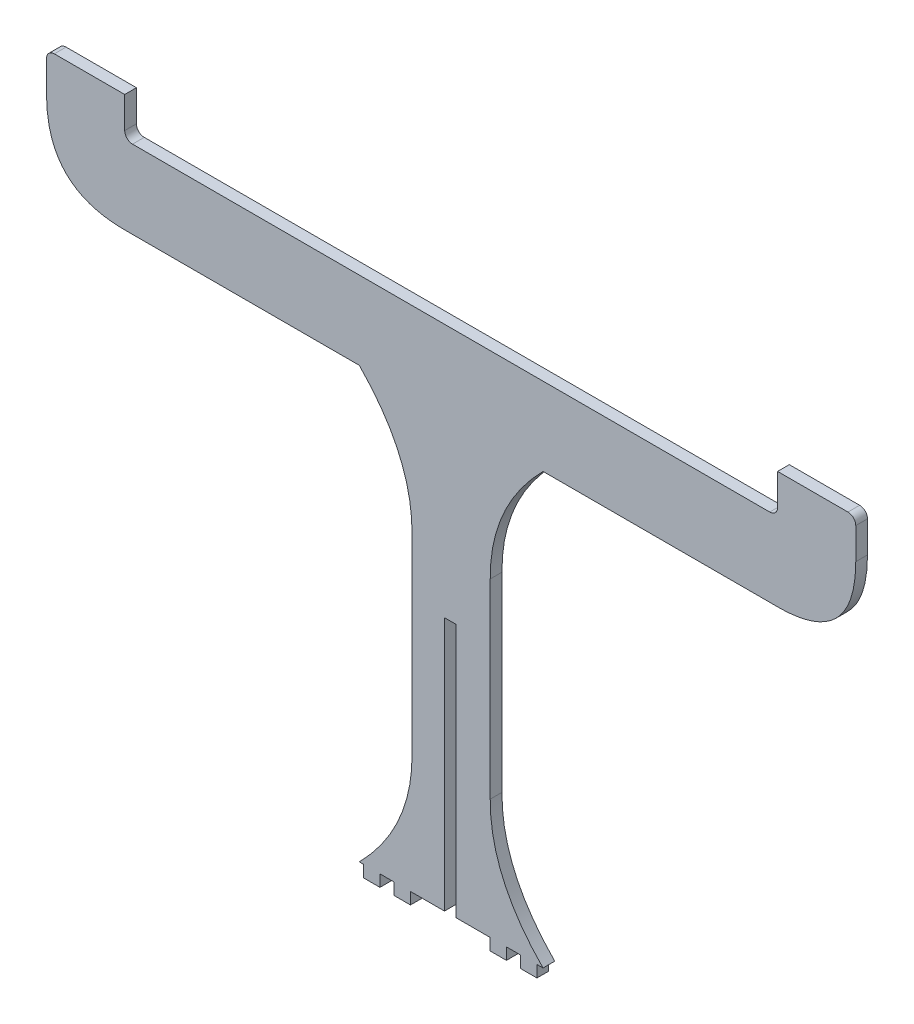
SolidWorks part; units mm, degrees
ref_plane "Přední rovina" through (0, 0, 0) normal (0, 0, 1) x (1, 0, 0)
ref_plane "Horní rovina" through (0, 0, 0) normal (0, 1, 0) x (1, 0, 0)
ref_plane "Pravá rovina" through (0, 0, 0) normal (1, 0, 0) x (0, 0, -1)
sketch "Skica1" plane through (0, 0, 0) normal (0, 0, 1) x (1, 0, 0)
  line L0 (-30.6426, 2.6943) -> (16.3574, 2.6943)
  line L1 (-7.1426, 2.6943) -> (-7.1426, -107.3057)
  line L2 (16.3574, -107.3057) -> (-30.6426, -107.3057)
  line L3 (-17.1426, 9.0001) -> (-17.1426, -176.0586) construction
  line L4 (27.2473, -27.3057) -> (-64.2445, -27.3057) construction
  line L5 (15.3668, -77.3057) -> (-64.2445, -77.3057) construction
  line L6 (-17.1426, -27.8784) -> (-17.1426, -76.656)
  line L7 (2.8574, -27.8784) -> (2.8574, -76.656)
  line L24 (-7.1426, -15.139) -> (-7.1426, 72.526) construction
  line L25 (10.652, -107.3057) -> (10.652, -110.3057)
  line L26 (10.652, -107.3057) -> (14.802, -107.3057)
  line L27 (14.802, -107.3057) -> (14.802, -110.3057)
  line L28 (10.652, -110.3057) -> (14.802, -110.3057)
  line L29 (2.852, -107.3057) -> (2.852, -110.3057)
  line L30 (2.852, -107.3057) -> (7.002, -107.3057)
  line L31 (7.002, -107.3057) -> (7.002, -110.3057)
  line L32 (2.852, -110.3057) -> (7.002, -110.3057)
  line L33 (-25.348, -110.3057) -> (-29.498, -110.3057)
  line L34 (-29.498, -107.3057) -> (-29.498, -110.3057)
  line L35 (-25.348, -107.3057) -> (-29.498, -107.3057)
  line L36 (-25.348, -107.3057) -> (-25.348, -110.3057)
  line L37 (-17.548, -110.3057) -> (-21.698, -110.3057)
  line L38 (-21.698, -107.3057) -> (-21.698, -110.3057)
  line L39 (-17.548, -107.3057) -> (-21.698, -107.3057)
  line L40 (-17.548, -107.3057) -> (-17.548, -110.3057)
  line L41 (-190.6426, 2.6943) -> (100.2644, 2.6943) construction
  line L42 (16.3574, 2.6943) -> (16.3574, 73.8241) construction
  line L43 (-30.6426, 73.8241) -> (-30.6426, 2.6943) construction
  line L44 (-110.6426, 2.6943) -> (-110.6426, 52.9232) construction
  line L45 (-190.6426, 32.6943) -> (86.9117, 32.6943) construction
  line L46 (-30.6426, 2.6943) -> (-90.6426, 2.6943)
  line L47 (-90.6426, -13.7924) -> (-90.6426, 96.8534) construction
  line L48 (-70.6426, -7.8313) -> (-70.6426, 84.4343) construction
  line L49 (-194.5635, 22.6943) -> (-7.1426, 22.6943) construction
  line L50 (-108.6426, 32.6943) -> (-90.6426, 32.6943)
  line L51 (-90.6426, 32.6943) -> (-90.6426, 24.6943)
  line L52 (-110.6426, 22.6943) -> (-110.6426, 30.6943)
  line L53 (16.3574, 2.6943) -> (76.3574, 2.6943)
  line L54 (-110.6426, 22.6943) -> (-110.6426, 2.6943) construction
  line L55 (76.3574, 32.6943) -> (76.3574, 24.6943)
  line L56 (-110.6426, 2.6943) -> (-90.6426, 2.6943) construction
  line L57 (94.3574, 32.6943) -> (76.3574, 32.6943)
  line L58 (-88.6426, 22.6943) -> (74.3574, 22.6943)
  line L59 (-7.1426, 22.6943) -> (-7.1426, 2.6943)
  line L60 (96.3574, 22.6943) -> (96.3574, 30.6943)
  line L61 (96.3574, 22.6943) -> (96.3574, 2.6943) construction
  line L62 (96.3574, 2.6943) -> (76.3574, 2.6943) construction
  arc A0 (74.3574, 22.6943) -> (76.3574, 24.6943) centre (74.3574, 24.6943) ccw
  arc A1 (-88.6426, 22.6943) -> (-90.6426, 24.6943) centre (-88.6426, 24.6943) cw
  arc A2 (-110.6426, 30.6943) -> (-108.6426, 32.6943) centre (-108.6426, 30.6943) cw
  arc A3 (96.3574, 30.6943) -> (94.3574, 32.6943) centre (94.3574, 30.6943) ccw
  spline S0 degree 2 poles (-30.6426, 2.6943) (-17.0251, -11.1181) (-17.1426, -27.8784) knots 0 0 0 1 1 1
  spline S1 degree 2 poles (-30.6426, -107.3057) (-17.0093, -93.4583) (-17.1426, -76.656) knots 0 0 0 1 1 1
  spline S2 degree 2 poles (16.3574, 2.6943) (2.7399, -11.1181) (2.8574, -27.8784) knots 0 0 0 1 1 1
  spline S3 degree 2 poles (16.3574, -107.3057) (2.724, -93.4583) (2.8574, -76.656) knots 0 0 0 1 1 1
  spline S4 degree 2 poles (-110.6426, 22.6943) (-110.6426, 2.6943) (-90.6426, 2.6943) knots 0 0 0 1 1 1
  spline S5 degree 2 poles (96.3574, 22.6943) (96.3574, 2.6943) (76.3574, 2.6943) knots 0 0 0 1 1 1
  point P29 (-110.6426, 2.6943)
  point P37 (-110.6426, 22.6943)
  point P54 (-110.6426, 32.6943)
  point P55 (-90.6426, 32.6943)
  point P56 (-90.6426, 22.6943)
  point P70 (-90.6426, 22.6943)
  point P73 (-110.6426, 32.6943)
  dimension "D15" = 60
  dimension "D17" = 2
  dimension "D18" = 2
  dimension "D1" = 110
  dimension "D2" = 23.5
  dimension "D3" = 30
  dimension "D4" = 30
  dimension "D5" = 30.6498
  dimension "D6" = 23.5
  dimension "D7" = 47
  dimension "D8" = 30
  dimension "D9" = 30
  dimension "D10" = 20
  dimension "D11" = 80
  dimension "D12" = 20
  dimension "D13" = 40
  dimension "D14" = 10
extrude "Přidat vysunutím2" add sketch "Skica1" along normal blind 3 contours S1 L2 L1 L0 S0 L6 | L2 S3 L7 S2 L0 L1 | L0 | L0 | L0 | L0 | L40 L2 L38 L37 | L36 L2 L34 L33 | L29 L32 L31 L2 | L25 L28 L27 L2 region at (-61.2298, 14.2338, 0) region at (-13.8581, -52.3107, 0) region at (46.9445, 14.2338, 0) region at (-0.4272, -52.3107, 0) region at (4.927, -108.8057, 0) region at (-19.623, -108.8057, 0) region at (-27.423, -108.8057, 0) region at (12.727, -108.8057, 0)
sketch "Skica2" plane through (0, 0, 0) normal (0, 0, -1) x (-1, 0, 0)
  line L0 (7.348, -179.4639) -> (7.348, -1.6157) construction
  line L1 (50.2587, -107.3057) -> (-73.7805, -107.3057) construction
  line L2 (-2.852, -107.3057) -> (17.548, -107.3057) construction
  line L5 (8.848, -107.3057) -> (5.848, -107.3057)
  line L8 (8.848, -42.3057) -> (5.848, -42.3057)
  line L9 (8.848, -42.3057) -> (8.848, -107.3057)
  line L10 (8.848, -107.3057) -> (5.848, -107.3057)
  line L11 (5.848, -42.3057) -> (5.848, -107.3057)
  line L12 (8.848, -42.3057) -> (5.848, -107.3057) construction
  line L13 (8.848, -107.3057) -> (5.848, -42.3057) construction
  line L15 (88.6426, 22.6943) -> (-74.3574, 22.6943) construction
  point P5 (7.348, -134.9898)
  point P7 (0, 0)
  point P8 (7.348, -74.8057)
  point P18 (5.848, -57.1217)
  dimension "D1" = 130
  dimension "D2" = 65
  dimension "D4" = 3
  dimension "D5" = 3
extrude "Odebrat vysunutím3" cut sketch "Skica2" against normal blind 3 contours L11 L10 L9 L8
